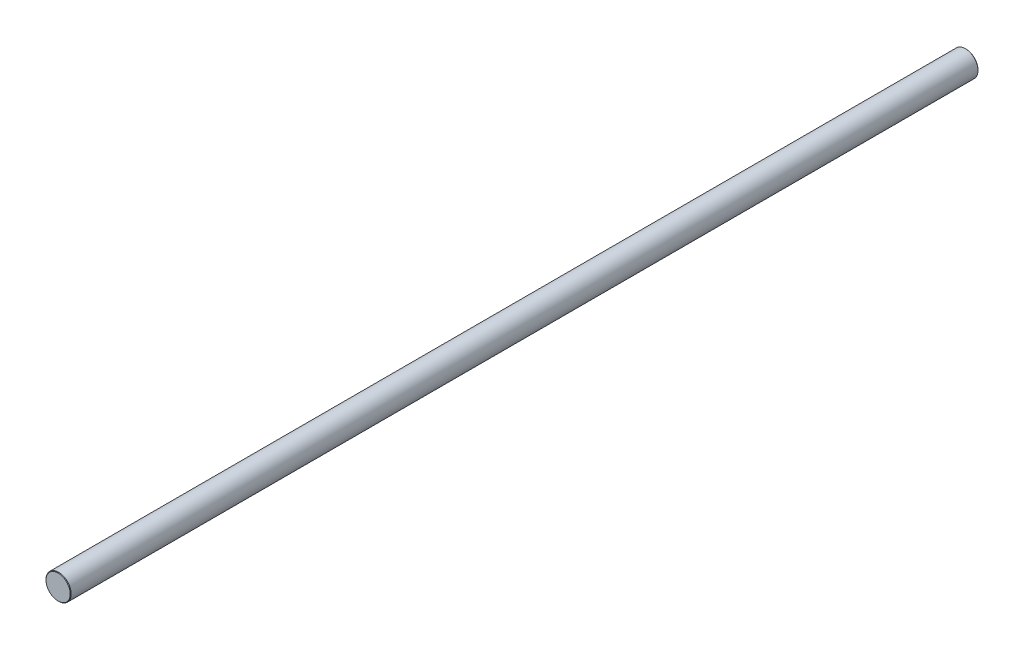
SolidWorks part; units mm, degrees
ref_plane "Front Plane" through (0, 0, 0) normal (0, 0, 1) x (1, 0, 0)
ref_plane "Top Plane" through (0, 0, 0) normal (0, 1, 0) x (1, 0, 0)
ref_plane "Right Plane" through (0, 0, 0) normal (1, 0, 0) x (0, 0, -1)
sketch "Sketch1" plane through (0, 0, 0) normal (0, 0, 1) x (1, 0, 0)
  circle A0 centre (0, 0) radius 6.35 construction
  dimension "Diameter" = 12.7
sketch "Sketch2" plane through (0, 0, 0) normal (1, 0, 0) x (0, 0, -1)
  line L0 (228.6, 0) -> (-228.6, 0) construction
  point P0 (-182.88, 0)
  point P3 (0, 0)
  point P4 (182.88, 0)
  point P6 (-160.02, 0)
  point P7 (160.02, 0)
  dimension "Length" = 457.2
  dimension "D1" = 45.72
  dimension "D2" = 45.72
  dimension "D3" = 68.58
  dimension "D4" = 68.58
sketch "Sketch3" plane through (0, 0, 0) normal (0, 0, 1) x (1, 0, 0)
  circle A0 centre (0, 0) radius 6.35 construction
  circle A1 centre (0, 0) radius 6.35
extrude "Boss-Extrude1" add sketch "Sketch3" along normal up to vertex (228.6 mm away) and the other way up to vertex (228.6 mm away) up to point (0, 0, 228.6) other way up to point (0, 0, -228.6)
chamfer "Chamfer1" distance 0.254 angle 45 2 edges at (6.35, 0, 228.6) (6.35, 0, -228.6)
equation "\"D1@Chamfer1\"=\"Diameter@Sketch1\"*.02"
equation "\"D1@Sketch2\"=\"D2@Sketch2\""
equation "\"D2@Sketch2\"=\"Length@Sketch2\"*.1"
equation "\"D3@Sketch2\"=\"Length@Sketch2\"*.15"
equation "\"D4@Sketch2\"=\"D3@Sketch2\""
